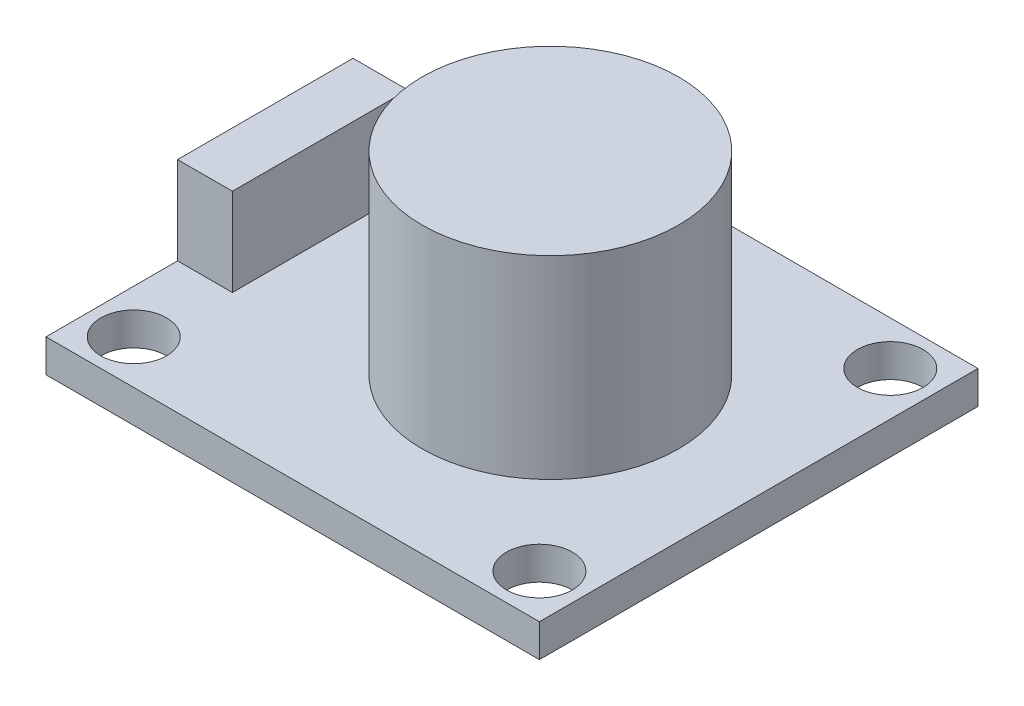
SolidWorks part; units mm, degrees
ref_plane "前视基准面" through (0, 0, 0) normal (0, 0, 1) x (1, 0, 0)
ref_plane "上视基准面" through (0, 0, 0) normal (0, 1, 0) x (1, 0, 0)
ref_plane "右视基准面" through (0, 0, 0) normal (1, 0, 0) x (0, 0, -1)
other "Configuration Table"
sketch "草图1" plane through (0, 0, 0) normal (0, 1, 0) x (1, 0, 0)
  line L1 (0, 0) -> (22.5, 0)
  line L2 (0, 0) -> (0, 20)
  line L3 (0, 20) -> (22.5, 20)
  line L4 (22.5, 0) -> (22.5, 20)
  line L5 (0, 14) -> (2.5, 14)
  line L6 (0, 14) -> (0, 6)
  line L7 (0, 6) -> (2.5, 6)
  line L8 (2.5, 14) -> (2.5, 6)
  circle A0 centre (2, 18) radius 1.5
  circle A1 centre (2, 2) radius 1.5
  circle A2 centre (20.5, 2) radius 1.5
  circle A3 centre (20.5, 18) radius 1.5
  circle A4 centre (13, 10) radius 5.85
  point P19 (0, 10)
  point P20 (2.5, 10)
  dimension "D3" = 11.7
  dimension "D6" = 3
  dimension "D1" = 22.5
  dimension "D2" = 20
  dimension "D4" = 2.5
  dimension "D5" = 8
  dimension "D7" = 2
  dimension "D8" = 2
  dimension "D9" = 2
  dimension "D10" = 2
  dimension "D11" = 9.5
extrude "凸台-拉伸1" add sketch "草图1" against normal blind 1.5 contours L5 L8 L7 L2 L1 L4 L3 A4 A3 A2 A1 A0 | A4 | L6 L5 L8 L7 region at (0.301, 0, -3)
extrude "凸台-拉伸2" add sketch "草图1<3>" along normal blind 8.84 contours A4 region at (13, 0, -10)
sketch "草图1<3>" plane through (0, 0, 0) normal (0, 1, 0) x (1, 0, 0) same geometry as "草图1"
extrude "凸台-拉伸3" add sketch "草图1<4>" along normal blind 4 contours L8 L5 L2 L7 region at (1.25, 0, -10)
sketch "草图1<4>" plane through (0, 0, 0) normal (0, 1, 0) x (1, 0, 0) same geometry as "草图1"
